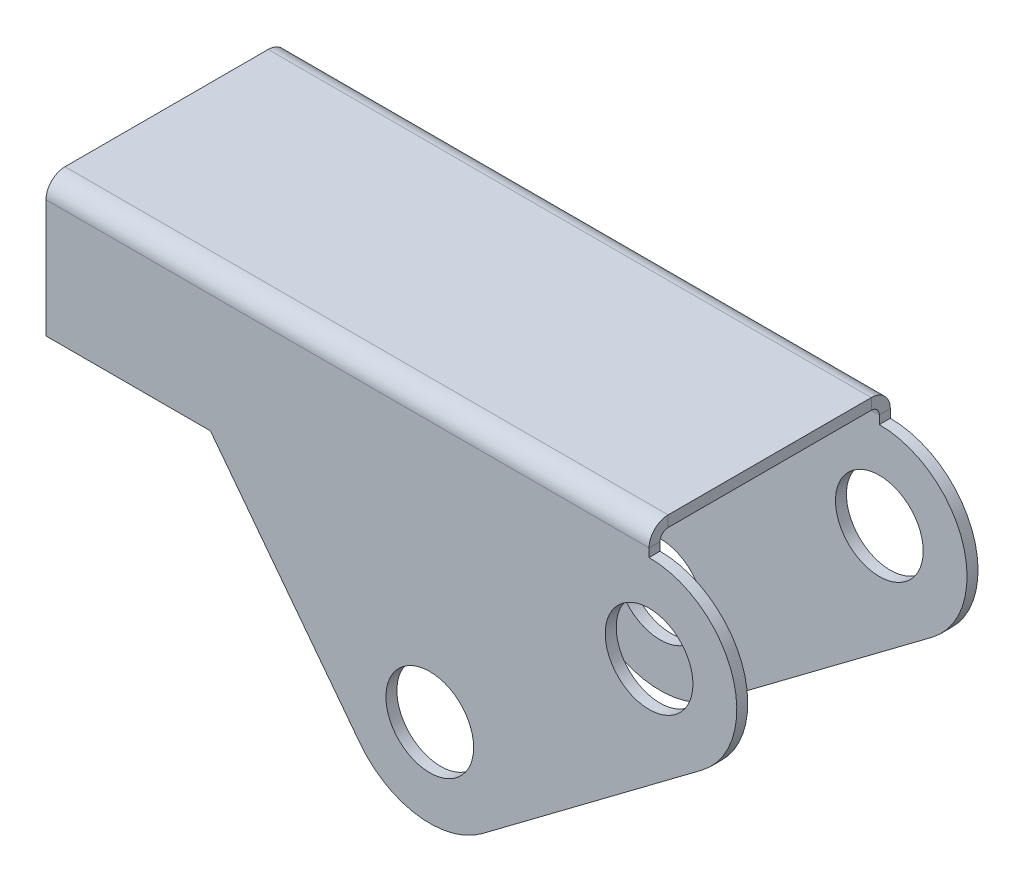
SolidWorks part; units mm, degrees
note: The reader was unsure of these and kept them because the rebuilt part matched: flange length of "Ребро-кромка2".
ref_plane "Спереди" through (0, 0, 0) normal (0, 0, 1) x (1, 0, 0)
ref_plane "Сверху" through (0, 0, 0) normal (0, 1, 0) x (1, 0, 0)
ref_plane "Справа" through (0, 0, 0) normal (1, 0, 0) x (0, 0, -1)
sketch "Эскиз1" plane through (0, 0, 0) normal (0, 0, 1) x (1, 0, 0)
  line L0 (20, 23) -> (-20, 23) construction
  line L1 (-20, 23) -> (-20, 13) construction
  line L2 (-20, 13) -> (-6.357, -4.8569)
  line L3 (4.8, -6.4) -> (24.8, 8.6)
  line L4 (-20, 23) -> (-20, 25.5) construction
  line L5 (-20, 25.5) -> (20, 25.5)
  line L6 (20, 25.5) -> (20, 23)
  line L7 (-20, 13) -> (-35, 13)
  line L8 (-35, 13) -> (-35, 25.5)
  line L9 (-35, 25.5) -> (-20, 25.5)
  circle A0 centre (0, 0) radius 4
  circle A1 centre (20, 15) radius 4
  arc A2 (24.8, 8.6) -> (20, 23) centre (20, 15) ccw
  arc A3 (-6.357, -4.8569) -> (4.8, -6.4) centre (0, 0) ccw
  point P15 (-20, 18)
  dimension "D5" = 8
  dimension "D6" = 8
  dimension "D1" = 20
  dimension "D2" = 15
  dimension "D3" = 4
  dimension "D4" = 4
  dimension "D7" = 10
  dimension "D8" = 20
  dimension "D9" = 2.5
  dimension "D10" = 15
base flange "Базовая кромка2" sketch "Эскиз1" thickness 1 reverse thickness direction no parameters "D1"=0.7366
edge flange "Ребро-кромка2" sketch "Эскиз15" flange angle 90 flange length 11 flange position material inside bend radius 0.7366 thickness 1 parameters "D6"=10
sketch "Эскиз15" plane through (0, 25.5, -1) normal (0, 1, 0) x (1, 0, 0)
  line L2 (-35, 0) -> (-35, 10)
  line L3 (-35, 10) -> (20, 10)
  line L4 (20, 10) -> (20, 0)
  line L7 (20, 0) -> (-35, 0) construction
  line L8 (20, 0) -> (-35, 0)
bend "EdgeBend2" bend radius 0.7366 bend angle 90 parameters "D5"=1
mirror "Зеркальное отражение1"
bend "Зеркальное отражение сгиба1" bend radius 0.7366 bend angle 90 parameters "D5"=2
sketch "Сгиб-Линии1" [suppressed] plane through (0, 0, 0) normal (0, 1, 0) x (1, 0, 0)
sketch "Граничная рамка1" [suppressed] plane through (0, 0, 0) normal (0, 1, 0) x (1, 0, 0)
sheet metal parameters "Листовой металл2" thickness 1 parameters "D1"=0.7366
flat pattern "Развертка2" [suppressed]
sketch "Сгиб-Линии3" plane through (0, 0, 0) normal (0, 1, 0) x (1, 0, 0)
sketch3d "Граничная рамка3" [suppressed]
  line L0 (-150, -59, 0) -> (8.9999, -59, 0) construction
  line L1 (-150, 12, 0) -> (8.9999, 12, 0) construction
  line L2 (-150, -59, 0) -> (-150, 12, 0) construction
  line L3 (8.9999, -59, 0) -> (8.9999, 12, 0) construction
sheet metal parameters "Листовой металл4" thickness 1 parameters "D1"=0.7366
flat pattern "Развертка2"
sketch "Сгиб-Линии3" plane through (0, 0, 0) normal (0, 0, 1) x (1, 0, 0)
  line L0 (50, 59.2346) -> (-100, 59.2346) construction
  line L1 (50, 59.2346) -> (-100, 59.2346) construction
sketch3d "Граничная рамка3" [suppressed]
  line L0 (-150, -59, 0) -> (8.9999, -59, 0) construction
  line L1 (-150, 18.4692, 0) -> (8.9999, 18.4692, 0) construction
  line L2 (-150, -59, 0) -> (-150, 18.4692, 0) construction
  line L3 (8.9999, -59, 0) -> (8.9999, 18.4692, 0) construction
bend of the flat pattern "Плоское состояние-<EdgeBend2>1"
sheet metal parameters "Листовой металл5" thickness 1 parameters "D1"=0.7366
flat pattern "Развертка5"
sketch "Сгиб-Линии4" plane through (0, 0, 0) normal (0, 0, 1) x (1, 0, 0)
  line L0 (20, 45.2039) -> (-35, 45.2039) construction
  line L1 (20, 24.7346) -> (-35, 24.7346) construction
  line L2 (20, 45.2039) -> (-35, 45.2039) construction
  line L3 (20, 24.7346) -> (-35, 24.7346) construction
sketch3d "Граничная рамка4" [suppressed]
  line L0 (8, 62.9384, 0) -> (8, -22.9999, 0) construction
  line L1 (-55, 62.9384, 0) -> (-55, -22.9999, 0) construction
  line L2 (8, 62.9384, 0) -> (-55, 62.9384, 0) construction
  line L3 (8, -22.9999, 0) -> (-55, -22.9999, 0) construction
bend of the flat pattern "Плоское состояние-<EdgeBend2>2"
bend of the flat pattern "Плоское состояние-<Зеркальное отражение сгиба1>1"
equation "\"Диаметр вала шестерни\" = 8  '!!!"
equation "\"Диаметр вала крепления\" = 8  '!!!"
equation "\"Межосевое прижима Вертикаль\" = 15  '!!!"
equation "\"Межосевое прижима Горизонталь\" = 20  '!!!"
equation "\"Толщина пластины прижима\" = 1  '!!!"
equation "\"D2@Эскиз1\"=\"Межосевое прижима Вертикаль\""
equation "\"D5@Эскиз1\"=\"Диаметр вала шестерни\""
equation "\"D6@Эскиз1\"=\"Диаметр вала крепления\""
equation "\"D9@Эскиз1\"=\"Толщина\"+1.5"
equation "\"D1@Эскиз1\"=\"Межосевое прижима Горизонталь\""
equation "\"D8@Эскиз1\"=\"D1@Эскиз1\""
equation "\"Ширина пластины прижима\" = 20  '!!!"
equation "\"D7@Ребро-кромка2\"=\"Ширина пластины прижима\"/2+\"Толщина\""
equation "\"D3@Эскиз1\"=\"D4@Эскиз1\""
